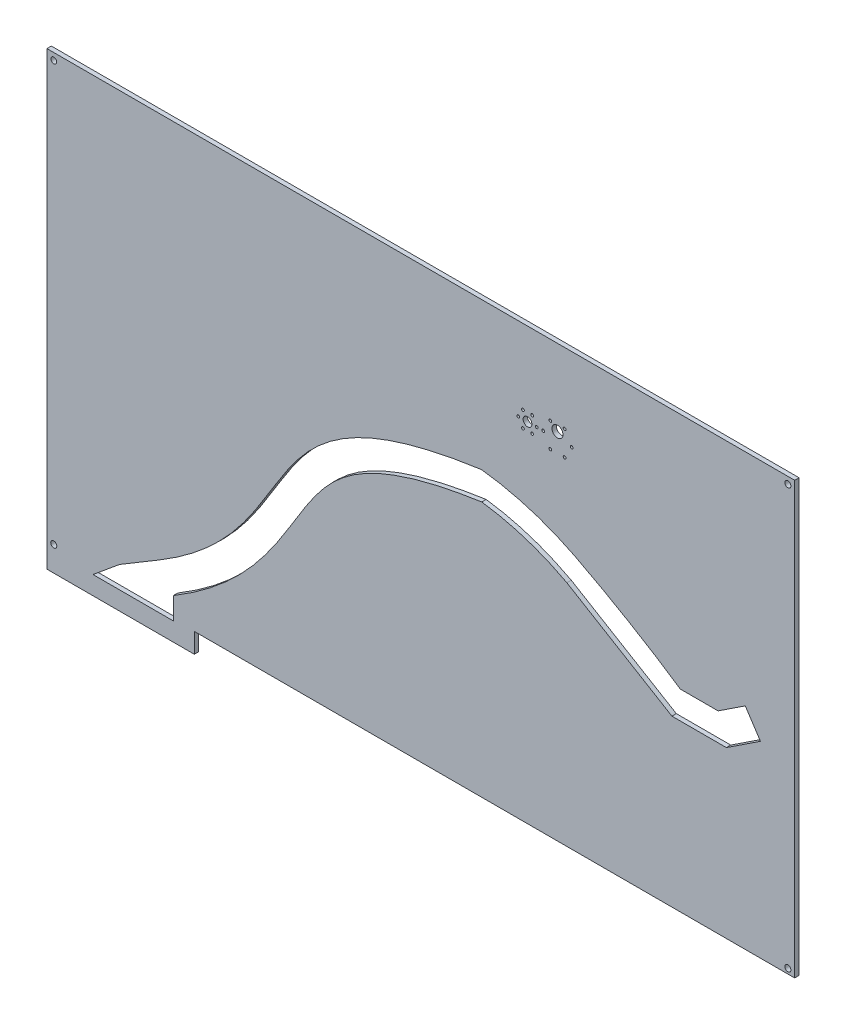
SolidWorks part; units mm, degrees
ref_plane "前视基准面" through (0, 0, 0) normal (0, 0, 1) x (1, 0, 0)
ref_plane "上视基准面" through (0, 0, 0) normal (0, 1, 0) x (1, 0, 0)
ref_plane "右视基准面" through (0, 0, 0) normal (1, 0, 0) x (0, 0, -1)
sketch "Sketch1" plane through (0, 0, 0) normal (0, 0, 1) x (1, 0, 0)
  line L0 (86.3892, 46.5642) -> (136.3892, 46.5642) construction
  line L1 (136.3892, 46.5642) -> (169.6686, 68.4983) construction
  line L2 (-475, -100) -> (-518.0311, -125.7444)
  line L3 (-459.5978, -125.7444) -> (-459.5978, -149.5504)
  line L4 (81.7745, 31.5642) -> (140.8878, 31.5642)
  line L5 (-467.2989, -112.8722) -> (-510.33, -138.6166) construction
  line L6 (140.8878, 31.5642) -> (177.9233, 55.9739)
  line L7 (-459.5978, -149.5504) -> (-546.7804, -149.5504)
  line L8 (-436.8168, -147.9944) -> (215.0808, -147.9944)
  line L9 (215.0808, -147.9944) -> (215.0808, 320)
  line L10 (215.0808, 320) -> (-596.8168, 320)
  line L11 (-596.8168, -150) -> (-596.8168, 320)
  line L12 (215.0808, -147.9944) -> (-596.8168, 320) construction
  line L13 (215.0808, 320) -> (-596.8168, -150) construction
  line L14 (-518.0311, -125.7444) -> (-459.5978, -125.7444) construction
  line L15 (-518.0311, -125.7444) -> (-546.7804, -149.5504)
  line L16 (-436.8168, -147.9944) -> (-436.8168, -169.5504)
  line L17 (90.9712, 61.5642) -> (131.8907, 61.5642)
  line L18 (-596.8168, -150) -> (-596.8168, -169.5504)
  line L19 (-596.8168, -169.5504) -> (-436.8168, -169.5504)
  line L21 (-32.3237, 100) -> (135.1953, 100) construction
  line L22 (-25, 130) -> (125, 130) construction
  line L23 (-28.6108, 115) -> (130.0228, 115) construction
  line L24 (131.8907, 61.5642) -> (161.4139, 81.0227)
  line L25 (177.9233, 55.9739) -> (161.4139, 81.0227)
  line L26 (-21.7014, 128.3139) -> (-25, 130)
  line L27 (-32.3237, 100) -> (81.7745, 31.5642)
  arc A0 (-125, 160) -> (-25, 130) centre (-159.8893, -137.9643) cw
  arc A1 (-28.6108, 115) -> (86.3892, 46.5642) centre (-559.3589, -907.7137) cw construction
  arc A2 (-124.7147, 129.7347) -> (-32.3237, 100) centre (-159.8893, -137.9643) cw
  circle A3 centre (-75, 230) radius 10 construction
  arc A4 (-124.84, 144.8723) -> (-28.6108, 115) centre (-159.8893, -137.9643) cw construction
  arc A5 (-21.7014, 128.3139) -> (90.9712, 61.5642) centre (-559.3589, -907.7137) cw
  circle A6 centre (-589.3757, -142.5578) radius 3.2924
  circle A7 centre (207.6422, -142.5578) radius 3.2924
  circle A8 centre (207.6422, 312.5578) radius 3.2944
  circle A9 centre (-589.3757, 312.5578) radius 3.1635
  arc A10 (135.1953, 100) -> (187.8618, 132.897) centre (303.6181, -111.0302) cw construction
  arc A11 (130.0228, 115) -> (181.4309, 146.4485) centre (303.6181, -111.0302) cw construction
  arc A12 (125, 130) -> (175, 160) centre (303.6181, -111.0302) cw construction
  arc A13 (-35.5202, 101.6861) -> (81.7745, 31.5642) centre (-559.3589, -907.7137) cw construction
  circle A14 centre (-85, 230) radius 1.5
  circle A15 centre (-80, 238.6603) radius 1.5
  circle A16 centre (-70, 238.6603) radius 1.5
  circle A17 centre (-65, 230) radius 1.5
  circle A18 centre (-70, 221.3397) radius 1.5
  circle A19 centre (-80, 221.3397) radius 1.5
  circle A20 centre (-42.5, 230) radius 15.5 construction
  circle A21 centre (-58, 230) radius 1.5
  circle A22 centre (-50.25, 243.4234) radius 1.5
  circle A23 centre (-34.75, 243.4234) radius 1.5
  circle A24 centre (-27, 230) radius 1.5
  circle A25 centre (-34.75, 216.5766) radius 1.5
  circle A26 centre (-50.25, 216.5766) radius 1.5
  circle A27 centre (-75, 230) radius 4.7625
  circle A28 centre (-42.5, 237) radius 6
  spline S0 degree 3 poles (-475, -100) (-419.5406, -66.8201) (-329.5908, 43.116) (-307.6356, 134.2871) (-125, 160) knots 0 0 0 0 0.312224 1 1 1 1
  spline S1 degree 1 poles (-459.5978, -125.7444) (-124.7147, 129.7347) knots 0 0 1 1 construction
  spline S2 degree 3 poles (-459.5978, -125.7444) (-458.1292, -124.8657) (-455.1858, -123.0815) (-449.4714, -119.5247) (-442.5555, -115.0462) (-434.6362, -109.6397) (-424.5564, -102.3861) (-412.8294, -93.2453) (-400.0558, -82.1905) (-388.4865, -71.0922) (-374.5374, -56.3046) (-359.6201, -37.9792) (-344.8908, -16.7676) (-332.3401, 3.2457) (-321.0552, 21.7964) (-310.226, 38.6648) (-299.0796, 53.8348) (-286.8128, 67.5146) (-272.4318, 80.0885) (-257.6527, 89.9241) (-243.4982, 97.442) (-231.5651, 102.8866) (-218.1727, 108.1127) (-203.191, 113.0878) (-189.2817, 116.9961) (-177.2434, 119.9629) (-167.7458, 122.1041) (-157.766, 124.1573) (-149.0369, 125.7919) (-141.7993, 127.0518) (-136.2431, 127.9723) (-131.5022, 128.7191) (-127.6487, 129.3032) (-125.6903, 129.5925) (-124.7147, 129.7347) knots 0 0 0 0 0.007773 0.015545 0.03109 0.046636 0.062181 0.093271 0.124361 0.155452 0.186542 0.248723 0.310904 0.373084 0.435265 0.497446 0.559626 0.621807 0.683988 0.746169 0.777259 0.808349 0.83944 0.87053 0.90162 0.917166 0.932711 0.948256 0.963801 0.971574 0.979346 0.987119 0.991005 0.994892 0.994892 0.994892 0.994892
  spline S3 degree 1 poles (-467.2989, -112.8722) (-124.84, 144.8723) knots 0 0 1 1 construction
  spline S4 degree 3 poles (-467.2989, -112.8722) (-465.8766, -112.0213) (-463.025, -110.2926) (-457.4973, -106.8516) (-450.8174, -102.5249) (-443.1848, -97.3122) (-433.4896, -90.3317) (-422.2436, -81.559) (-410.0336, -70.981) (-398.9994, -60.3828) (-385.707, -46.2708) (-371.4731, -28.7597) (-357.2741, -8.2881) (-344.9599, 11.3612) (-333.6257, 29.9919) (-322.417, 47.4318) (-310.4985, 63.6121) (-297.0179, 78.5777) (-281.0248, 92.4603) (-264.7088, 103.2127) (-249.3105, 111.3089) (-236.4572, 117.1105) (-222.1723, 122.621) (-206.3349, 127.8161) (-191.7467, 131.8615) (-179.1859, 134.915) (-169.3063, 137.1107) (-158.9544, 139.2089) (-149.9221, 140.8739) (-142.4479, 142.1541) (-136.7117, 143.0887) (-130.8627, 143.9946) (-126.8382, 144.5862) (-124.84, 144.8723) knots 0 0 0 0 0.007793 0.015586 0.031173 0.046759 0.062345 0.093518 0.12469 0.155863 0.187036 0.249381 0.311726 0.374071 0.436417 0.498762 0.561107 0.623452 0.685798 0.748143 0.779315 0.810488 0.841661 0.872833 0.904006 0.919592 0.935179 0.950765 0.966351 0.974144 0.981937 0.989731 0.997524 0.997524 0.997524 0.997524 construction
  point P38 (-190, 85.5025)
  point P62 (-75, 230)
  dimension "D5" = 300
  dimension "D8" = 15
  dimension "D14" = 470
  dimension "D18" = 70
  dimension "D19" = 31
  dimension "D20" = 3
  dimension "D21" = 6
  dimension "D22" = 651.8975
  dimension "D23" = 32.5
  dimension "D24" = 50
  dimension "D26" = 6
  dimension "D27" = 3
  dimension "D29" = 20
  dimension "D30" = 9.525
  dimension "D1" = 105
  dimension "D2" = 100
  dimension "D3" = 350
  dimension "D4" = 260
  dimension "D6" = 100
  dimension "D7" = 30
  dimension "D9" = 15
  dimension "D10" = 115
  dimension "D11" = 50
  dimension "D13" = 15
  dimension "D15" = 190
  dimension "D16" = 320
  dimension "D17" = 20
  dimension "D25" = 811.9
  dimension "D28" = 70
  dimension "D12" = 30
extrude "Boss-Extrude1" add sketch "Sketch1" along normal blind 4.7625
